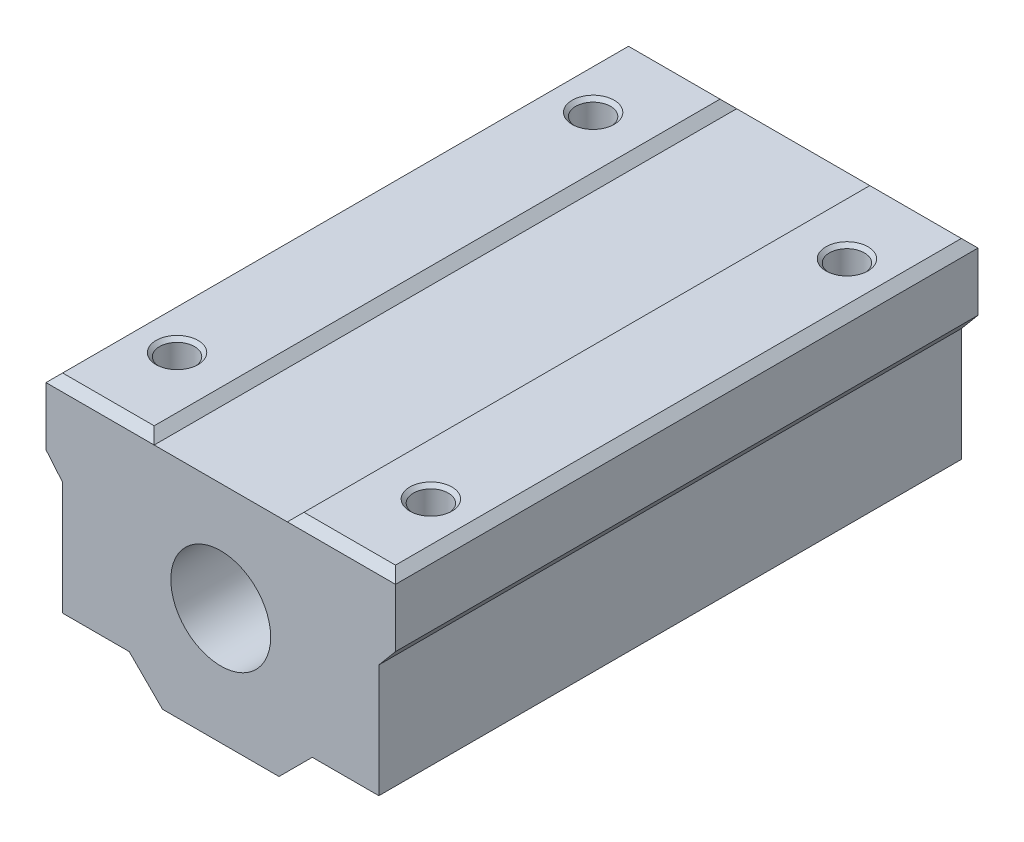
SolidWorks part; units mm, degrees
ref_plane "Plano frontal" through (0, 0, 0) normal (0, 0, 1) x (1, 0, 0)
ref_plane "Plano superior" through (0, 0, 0) normal (0, 1, 0) x (1, 0, 0)
ref_plane "Plano direito" through (0, 0, 0) normal (1, 0, 0) x (0, 0, -1)
sketch "Esboço1" plane through (0, 0, 0) normal (0, 0, 1) x (1, 0, 0)
  line L0 (0, 14) -> (0, -14) construction
  line L1 (8, 13) -> (-8, 13)
  line L2 (21, 14) -> (21, 6)
  line L3 (21, 6) -> (19, 3.6165)
  line L4 (19, 3.6165) -> (19, -10)
  line L5 (19, -10) -> (11, -10)
  line L6 (11, -10) -> (7, -14)
  line L7 (7, -14) -> (-7, -14)
  line L8 (8, 13) -> (8, 14)
  line L9 (8, 14) -> (21, 14)
  line L10 (-8, 14) -> (-21, 14)
  line L11 (-8, 13) -> (-8, 14)
  line L12 (-11, -10) -> (-7, -14)
  line L13 (-19, -10) -> (-11, -10)
  line L14 (-19, 3.6165) -> (-19, -10)
  line L15 (-21, 6) -> (-19, 3.6165)
  line L16 (-21, 14) -> (-21, 6)
  circle A0 centre (0, 0) radius 6
  point P21 (0, 13)
  dimension "D11" = 12
  dimension "D1" = 21
  dimension "D2" = 13
  dimension "D3" = 8
  dimension "D4" = 28
  dimension "D5" = 7
  dimension "D6" = 135
  dimension "D7" = 1
  dimension "D8" = 220
  dimension "D9" = 24
  dimension "D10" = 19
extrude "Ressalto-extrusão1" add sketch "Esboço1" against normal blind 70
chamfer "Chanfro1" distance 1 angle 45 8 edges at (14.5, 14, -70) (21, 14, -35) (14.5, 14, 0) (8, 14, -35) (-14.5, 14, -70) (-21, 14, -35) (-14.5, 14, 0) (-8, 14, -35)
hole_wizard "Furo roscado de M51" positions "Esboço2" profile "Esboço3" tap size "M5" standard "DIN" end condition through all
sketch "Esboço2" plane through (0, 14, 0) normal (0, 1, 0) x (1, 0, 0)
  line L0 (-21, 0) -> (-21, 70) construction
  line L1 (-8, 0) -> (-21, 0) construction
  point P0 (15.25, 10)
  point P2 (15.25, 60)
  point P4 (-15.25, 60)
  point P6 (-15.25, 10)
  point P9 (0, 0)
  point P10 (0, 0)
  dimension "D1" = 30.5
  dimension "D2" = 5.75
  dimension "D3" = 50
  dimension "D4" = 10
sketch "Esboço3" plane through (15.25, 14, -10) normal (1, 0, 0) x (0, 0, 1)
  line L0 (0, 0) -> (0, 28)
  line L1 (0, 28) -> (2.1, 28)
  line L2 (2.1, 28) -> (2.1, 0.425)
  line L3 (2.1, 0.425) -> (2.525, 0)
  line L5 (2.525, 0) -> (0, 0)
  line L6 (-2.1, 0.425) -> (-2.525, 0) construction
  line L11 (0, -6.35) -> (0, 107.95) construction
  dimension "Thru Tap Drill Dia." = 4.2
  dimension "Thru Tap Drill Depth" = 28
  dimension "Near C'Sink Dia." = 5.05
  dimension "Near C'Sink Angle" = 90
cosmetic thread "Rosca de furo1" parameters "D1"=12, "D2"=5
cosmetic thread "Rosca de furo2" parameters "D1"=12, "D2"=5
cosmetic thread "Rosca de furo3" parameters "D1"=12, "D2"=5
cosmetic thread "Rosca de furo4" parameters "D1"=12, "D2"=5
chamfer "Chanfro2" distance 1 angle 45 4 edges at (17.35, -10, -60) (-15.25, -10, -62.1) (-15.25, -10, -12.1) (17.35, -10, -10)
